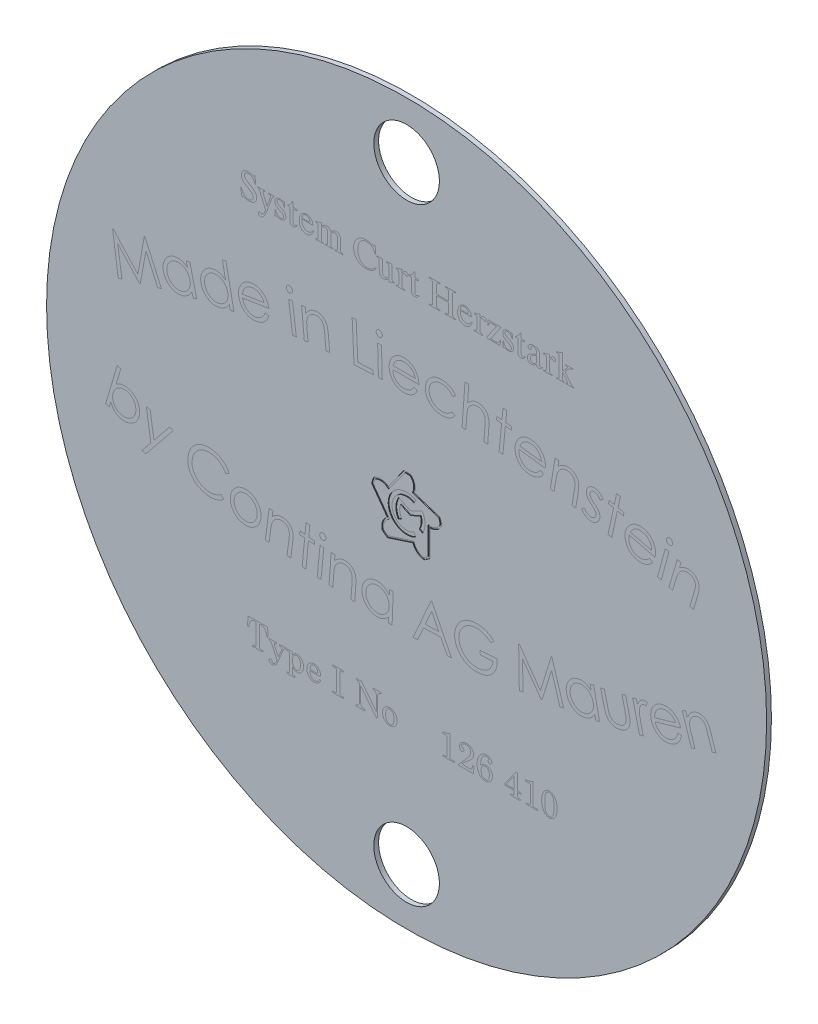
SolidWorks part; units mm, degrees
ref_plane "Front Plane" through (0, 0, 0) normal (0, 0, 1) x (1, 0, 0)
ref_plane "Top Plane" through (0, 0, 0) normal (0, 1, 0) x (1, 0, 0)
ref_plane "Right Plane" through (0, 0, 0) normal (1, 0, 0) x (0, 0, -1)
sketch "Sketch1" plane through (0, 0, 0) normal (0, 0, 1) x (1, 0, 0)
  circle A0 centre (0, 0) radius 22.5
  dimension "D1" = 45
extrude "Boss-Extrude1" add sketch "Sketch1" against normal blind 0.3
hole_wizard "Ø4.1 (4.1) Diameter Hole1" positions "Sketch3" profile "Sketch2" hole size "Ø4.1" standard "DIN" end condition up to next
sketch "Sketch3" plane through (0, 0, 0) normal (0, 0, 1) x (1, 0, 0)
  circle A0 centre (0, 0) radius 19 construction
  point P4 (0, 19)
  point P6 (0, -19)
  dimension "D1" = 38
sketch "Sketch2" plane through (0, 19, 0) normal (1, 0, 0) x (0, -1, 0)
  line L0 (0, 0) -> (0, 0.3)
  line L1 (0, 0.3) -> (2.05, 0.3)
  line L2 (2.05, 0.3) -> (2.05, 0)
  line L5 (2.05, 0) -> (0, 0)
  line L11 (0, -6.35) -> (0, 107.95) construction
  dimension "Thru Hole Dia." = 4.1
  dimension "Thru Hole Depth" = 0.3
sketch "Sketch4" plane through (0, 0, 0) normal (0, 0, 1) x (1, 0, 0)
  line L0 (0, 0) -> (0, 22.5) construction
  line L1 (-11, 12) -> (11, 12) construction
  line L2 (0, 0) -> (-22.5, 0) construction
  line L3 (-10, -12) -> (0, -12) construction
  line L4 (2, -12) -> (10, -12) construction
  circle A0 centre (0, 0) radius 22.5 construction
  arc A1 (-19.0749, 3.3872) -> (19.0749, 3.3872) centre (0, -53.5) cw construction
  arc A2 (-19.0749, -3.3872) -> (19.0749, -3.3872) centre (0, 53.5) ccw construction
  text T0 "System Curt Herzstark" font "Dutch801 Rm BT" height 1.5
  text T1 "Made in Liechtenstein" font "Century Gothic" height 2.5
  text T2 "by Contina AG Mauren" font "Century Gothic" height 2.5
  text T3 "Type I No " font "Century Schoolbook" height 1.5
  text T4 "126 410" font "Century Schoolbook" height 1.5
  dimension "D3" = 6.5
  dimension "D4" = 60
  dimension "D1" = 12
  dimension "D2" = 22
  dimension "D5" = 12
  dimension "D6" = 10
  dimension "D7" = 2
  dimension "D8" = 10
wrap "Wrap1" sketch "Sketch4" wrap type scribe source sketch "Sketch4" face at (2.05, 19, 0)
sketch "Sketch5" plane through (0, 0, 0) normal (0, 0, 1) x (1, 0, 0)
  line L0 (0, 0) -> (0, 3.4654) construction
  line L1 (0, 0) -> (1.4, 0) construction
  line L2 (0.455, 0.7881) -> (0.575, 0.9959)
  line L3 (0.455, -0.7881) -> (0.575, -0.9959)
  line L4 (0.455, 0.7881) -> (0, 0) construction
  line L5 (0.24, 0.2648) -> (-0.4961, 0.6081)
  line L6 (0.24, 0.2648) -> (0.24, 0.6223) construction
  line L7 (0.24, 0.2648) -> (0.9761, 0.6081)
  line L8 (0.24, 0) -> (-0.3825, 0.2903)
  line L9 (0.24, 0) -> (0.8625, 0.2903)
  line L10 (0.24, 0.2648) -> (0.9036, 0.5743) construction
  line L11 (0.24, 0) -> (0.7309, 0.2289) construction
  line L12 (0.7881, -0.455) -> (0.9959, -0.575)
  line L13 (0, 0) -> (0.7881, -0.455) construction
  line L14 (0.24, 0) -> (-0.2509, 0.2289) construction
  line L15 (0.24, 0.2648) -> (-0.4236, 0.5743) construction
  line L16 (-0.5159, -0.575) -> (-0.3081, -0.455)
  line L17 (-0.1351, 2.1958) -> (-1.1326, 0.8229)
  line L18 (2.0466, 0.8071) -> (0.4326, 1.3315)
  line L19 (1.4, -1.6971) -> (1.4, 0)
  line L20 (-1.1814, -1.8559) -> (0.4326, -1.3315)
  line L21 (-2.1301, 0.55) -> (-1.1326, -0.8229)
  arc A0 (0.575, 0.9959) -> (0.575, -0.9959) centre (0, 0) ccw
  arc A1 (0.455, 0.7881) -> (0.455, -0.7881) centre (0, 0) ccw
  arc A2 (0.8625, 0.2903) -> (0.7881, -0.455) centre (0, 0) cw
  circle A3 centre (0, 0) radius 0.91 construction
  circle A4 centre (0, 0) radius 1.15 construction
  arc A5 (0.9761, 0.6081) -> (0.9959, -0.575) centre (0, 0) cw
  arc A6 (-0.4236, 0.5743) -> (0.9036, 0.5743) centre (0.24, 0.2648) ccw construction
  arc A7 (-0.2509, 0.2289) -> (0.7309, 0.2289) centre (0.24, 0.2648) ccw construction
  arc A8 (-0.3825, 0.2903) -> (-0.3081, -0.455) centre (0.48, 0) ccw
  arc A9 (-0.4961, 0.6081) -> (-0.5159, -0.575) centre (0.48, 0) ccw
  arc A10 (0.2482, 2.186) -> (-0.1351, 2.1958) centre (0, 0) ccw
  arc A11 (0.4326, 1.3315) -> (0.2482, 2.186) centre (-0.2554, 1.6301) ccw
  arc A12 (2.1557, 0.4395) -> (2.0466, 0.8071) centre (0, 0) ccw
  arc A13 (1.4, 0) -> (2.1557, 0.4395) centre (1.4714, 0.7466) ccw
  arc A14 (1.0841, -1.9144) -> (1.4, -1.6971) centre (0, 0) ccw
  arc A15 (0.4326, -1.3315) -> (1.0841, -1.9144) centre (1.1647, -1.1687) ccw
  arc A16 (-1.4857, -1.6226) -> (-1.1814, -1.8559) centre (0, 0) ccw
  arc A17 (-1.1326, -0.8229) -> (-1.4857, -1.6226) centre (-0.7516, -1.4689) ccw
  arc A18 (-2.0023, 0.9115) -> (-2.1301, 0.55) centre (0, 0) ccw
  arc A19 (-1.1326, 0.8229) -> (-2.0023, 0.9115) centre (-1.6292, 0.2609) ccw
  point P6 (1.0519, 0.3216)
  point P11 (0.8224, 0.2514)
  dimension "D1" = 0.24
  dimension "D2" = 2.3
  dimension "D4" = 130
  dimension "D7" = 30
  dimension "D3" = 120
  dimension "D6" = 0.24
  dimension "D5" = 0.24
sketch "Sketch6" plane through (0, 0, 0) normal (0, 0, 1) x (1, 0, 0)
  line L0 (2.0466, 0.8071) -> (0.4326, 1.3315) construction
  line L1 (-0.1351, 2.1958) -> (-1.1326, 0.8229) construction
  line L2 (-2.1301, 0.55) -> (-1.1326, -0.8229) construction
  line L3 (-1.1814, -1.8559) -> (0.4326, -1.3315) construction
  line L4 (1.4, -1.6971) -> (1.4, 0) construction
  line L5 (2.0466, 0.8071) -> (0.4326, 1.3315)
  line L6 (-0.1351, 2.1958) -> (-1.1326, 0.8229)
  line L7 (-2.1301, 0.55) -> (-1.1326, -0.8229)
  line L8 (-1.1814, -1.8559) -> (0.4326, -1.3315)
  line L9 (1.4, -1.6971) -> (1.4, 0)
  arc A0 (0.4326, 1.3315) -> (0.2482, 2.186) centre (-0.2554, 1.6301) ccw construction
  arc A1 (0.2482, 2.186) -> (-0.1351, 2.1958) centre (0, 0) ccw construction
  arc A2 (-1.1326, 0.8229) -> (-2.0023, 0.9115) centre (-1.6292, 0.2609) ccw construction
  arc A3 (-2.0023, 0.9115) -> (-2.1301, 0.55) centre (0, 0) ccw construction
  arc A4 (-1.1326, -0.8229) -> (-1.4857, -1.6226) centre (-0.7516, -1.4689) ccw construction
  arc A5 (-1.4857, -1.6226) -> (-1.1814, -1.8559) centre (0, 0) ccw construction
  arc A6 (0.4326, -1.3315) -> (1.0841, -1.9144) centre (1.1647, -1.1687) ccw construction
  arc A7 (1.0841, -1.9144) -> (1.4, -1.6971) centre (0, 0) ccw construction
  arc A8 (1.4, 0) -> (2.1557, 0.4395) centre (1.4714, 0.7466) ccw construction
  arc A9 (2.1557, 0.4395) -> (2.0466, 0.8071) centre (0, 0) ccw construction
  arc A10 (0.4326, 1.3315) -> (0.2482, 2.186) centre (-0.2554, 1.6301) ccw
  arc A11 (0.2482, 2.186) -> (-0.1351, 2.1958) centre (0, 0) ccw
  arc A12 (-1.1326, 0.8229) -> (-2.0023, 0.9115) centre (-1.6292, 0.2609) ccw
  arc A13 (-2.0023, 0.9115) -> (-2.1301, 0.55) centre (0, 0) ccw
  arc A14 (-1.1326, -0.8229) -> (-1.4857, -1.6226) centre (-0.7516, -1.4689) ccw
  arc A15 (-1.4857, -1.6226) -> (-1.1814, -1.8559) centre (0, 0) ccw
  arc A16 (0.4326, -1.3315) -> (1.0841, -1.9144) centre (1.1647, -1.1687) ccw
  arc A17 (1.0841, -1.9144) -> (1.4, -1.6971) centre (0, 0) ccw
  arc A18 (1.4, 0) -> (2.1557, 0.4395) centre (1.4714, 0.7466) ccw
  arc A19 (2.1557, 0.4395) -> (2.0466, 0.8071) centre (0, 0) ccw
extrude "Cut-Extrude-Thin2" cut sketch "Sketch6" against normal blind 0.05 thin thin type mid plane wall 0.1
sketch "Sketch7" plane through (0, 0, 0) normal (0, 0, 1) x (1, 0, 0)
  line L2 (0.455, 0.7881) -> (0.575, 0.9959)
  line L3 (0.575, -0.9959) -> (0.455, -0.7881)
  line L4 (0.455, 0.7881) -> (0.575, 0.9959)
  line L5 (0.575, -0.9959) -> (0.455, -0.7881)
  line L10 (0.24, 0.2648) -> (-0.4961, 0.6081)
  line L11 (0.9761, 0.6081) -> (0.24, 0.2648)
  line L12 (0.7881, -0.455) -> (0.9959, -0.575)
  line L13 (0.24, 0) -> (0.8625, 0.2903)
  line L14 (-0.3825, 0.2903) -> (0.24, 0)
  line L15 (-0.5159, -0.575) -> (-0.3081, -0.455)
  line L16 (0.24, 0.2648) -> (-0.4961, 0.6081)
  line L17 (0.9761, 0.6081) -> (0.24, 0.2648)
  line L18 (0.7881, -0.455) -> (0.9959, -0.575)
  line L19 (0.24, 0) -> (0.8625, 0.2903)
  line L20 (-0.3825, 0.2903) -> (0.24, 0)
  line L21 (-0.5159, -0.575) -> (-0.3081, -0.455)
  arc A2 (0.575, 0.9959) -> (0.575, -0.9959) centre (0, 0) ccw
  arc A3 (0.455, 0.7881) -> (0.455, -0.7881) centre (0, 0) ccw
  arc A4 (0.575, 0.9959) -> (0.575, -0.9959) centre (0, 0) ccw
  arc A5 (0.455, 0.7881) -> (0.455, -0.7881) centre (0, 0) ccw
  arc A8 (0.9959, -0.575) -> (0.9761, 0.6081) centre (0, 0) ccw
  arc A9 (0.7881, -0.455) -> (0.8625, 0.2903) centre (0, 0) ccw
  arc A10 (-0.3825, 0.2903) -> (-0.3081, -0.455) centre (0.48, 0) ccw
  arc A11 (-0.4961, 0.6081) -> (-0.5159, -0.575) centre (0.48, 0) ccw
  arc A12 (0.9959, -0.575) -> (0.9761, 0.6081) centre (0, 0) ccw
  arc A13 (0.7881, -0.455) -> (0.8625, 0.2903) centre (0, 0) ccw
  arc A14 (-0.3825, 0.2903) -> (-0.3081, -0.455) centre (0.48, 0) ccw
  arc A15 (-0.4961, 0.6081) -> (-0.5159, -0.575) centre (0.48, 0) ccw
  dimension "D1" = 0
  dimension "D2" = 0
extrude "Cut-Extrude1" cut sketch "Sketch7" against normal blind 0.05
